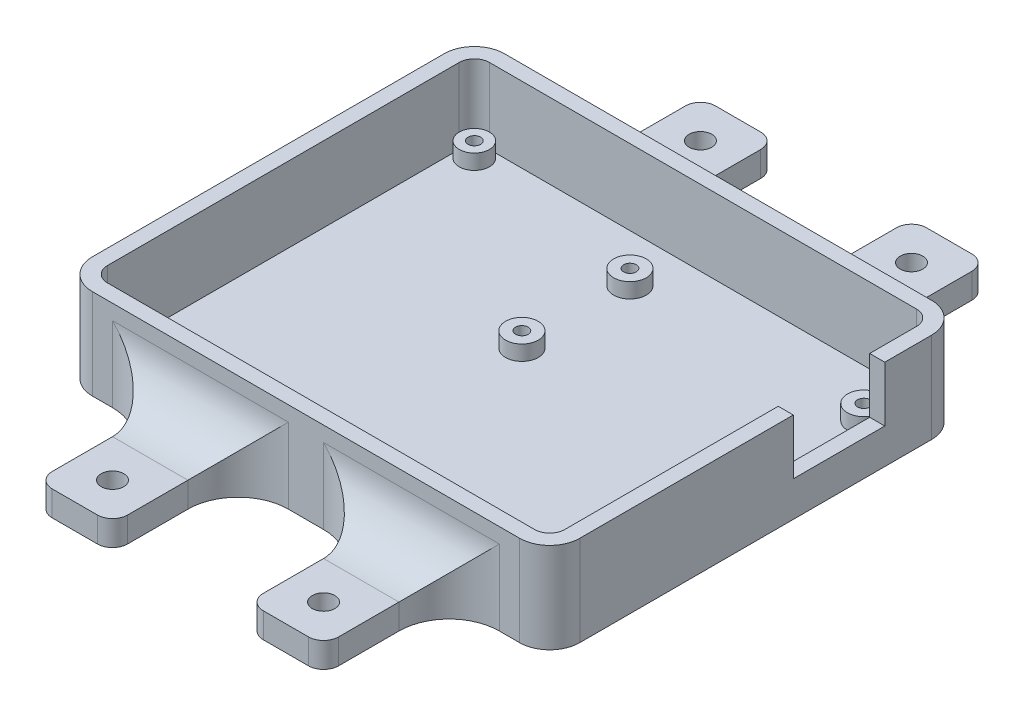
SolidWorks part; units mm, degrees
ref_plane "Front Plane" through (0, 0, 0) normal (0, 0, 1) x (1, 0, 0)
ref_plane "Top Plane" through (0, 0, 0) normal (0, 1, 0) x (1, 0, 0)
ref_plane "Right Plane" through (0, 0, 0) normal (1, 0, 0) x (0, 0, -1)
sketch "Sketch1" plane through (0, 0, 0) normal (0, 1, 0) x (1, 0, 0)
  line L0 (-3, 3) -> (-88, 3)
  line L1 (-3, 0) -> (-88, 0)
  line L2 (0, -3) -> (0, -73)
  line L3 (-3, -76) -> (-88, -76)
  line L4 (-91, -3) -> (-91, -73)
  line L5 (-94, -3) -> (-94, -73)
  line L6 (-3, -79) -> (-88, -79)
  line L7 (3, -3) -> (3, -73)
  circle A0 centre (-3.99, -9.5) radius 1.25
  circle A1 centre (-50.53, -9.5) radius 1.25
  circle A2 centre (-3.99, -31) radius 1.25
  circle A3 centre (-50.53, -31) radius 1.25
  arc A4 (0, -73) -> (-3, -76) centre (-3, -73) cw
  arc A5 (-88, -76) -> (-91, -73) centre (-88, -73) cw
  arc A6 (-88, 0) -> (-91, -3) centre (-88, -3) ccw
  arc A7 (-3, 0) -> (0, -3) centre (-3, -3) cw
  circle A8 centre (-3.99, -9.5) radius 3.25
  circle A9 centre (-3.99, -31) radius 3.25
  circle A10 centre (-50.53, -31) radius 3.25
  circle A11 centre (-50.53, -9.5) radius 3.25
  circle A12 centre (-3, -3) radius 1.25
  circle A13 centre (-88, -3) radius 1.25
  circle A14 centre (-88, -73) radius 1.25
  circle A15 centre (-3, -73) radius 1.25
  circle A16 centre (-3, -3) radius 3
  circle A17 centre (-3, -73) radius 3
  circle A18 centre (-88, -73) radius 3
  circle A19 centre (-88, -3) radius 3
  arc A20 (-88, 3) -> (-94, -3) centre (-88, -3) ccw
  arc A21 (-88, -79) -> (-94, -73) centre (-88, -73) cw
  arc A22 (3, -73) -> (-3, -79) centre (-3, -73) cw
  arc A23 (-3, 3) -> (3, -3) centre (-3, -3) cw
  point P21 (0, -76)
  point P26 (-91, 0)
  point P29 (0, 0)
  dimension "D1" = 2.5
  dimension "D2" = 2.5
  dimension "D3" = 2.5
  dimension "D4" = 2.5
  dimension "D11" = 3
  dimension "D13" = 2.5
  dimension "D14" = 2.5
  dimension "D15" = 2.5
  dimension "D16" = 2.5
  dimension "D5" = 21.5
  dimension "D6" = 46.54
  dimension "D7" = 9.5
  dimension "D8" = 3.99
  dimension "D9" = 76
  dimension "D10" = 91
  dimension "D18" = 3
  dimension "D12" = 2
  dimension "D17" = 1.75
extrude "Boss-Extrude1" add sketch "Sketch1" against normal blind 3 contours L0 A20 L5 A21 L6 A22 L7 A23
extrude "Boss-Extrude2" add sketch "Sketch1<4>" along normal blind 15 contours A23 L0 A20 L5 A21 L6 A22 L7 L1 A7 L2 A4 L3 A5 L4 A6 region at (0.3445, 0, -0.3445)
sketch "Sketch1<4>" plane through (0, 0, 0) normal (0, 1, 0) x (1, 0, 0) same geometry as "Sketch1"
extrude "Boss-Extrude3" add sketch "Sketch1<5>" along normal blind 3 contours A6 A19 A13 | A11 A1 | A10 A3 | A7 A16 A12 | A8 A0 | A9 A2 | A4 A17 A15 | A5 A18 A14 region at (-0.9387, 0, 0.9387) region at (-85.9387, 0, 0.9387) region at (-0.9387, 0, 75.0613) region at (-88, 0, 70.0849) region at (-7.1481, 0, 9.5) region at (-7.1481, 0, 31) region at (-53.6881, 0, 31) region at (-53.6881, 0, 9.5)
sketch "Sketch1<5>" plane through (0, 0, 0) normal (0, 1, 0) x (1, 0, 0) same geometry as "Sketch1"
extrude "Cut-Extrude1" cut sketch "Sketch1<6>" against normal through all contours A13 | A1 | A3 | A12 | A0 | A2 | A15 | A14
sketch "Sketch1<6>" plane through (0, 0, 0) normal (0, 1, 0) x (1, 0, 0) same geometry as "Sketch1"
sketch "Sketch3" plane through (3, 0, 0) normal (1, 0, 0) x (0, 0, -1)
  line L0 (-3, -3) -> (-3, 15) construction
  line L1 (-30.52, 15) -> (-12.32, 15)
  line L2 (-30.52, 15) -> (-30.52, 4)
  line L3 (-30.52, 4) -> (-12.32, 4)
  line L4 (-12.32, 15) -> (-12.32, 4)
  line L5 (-3, -3) -> (-73, -3) construction
  line L6 (-3, 15) -> (-73, 15) construction
  dimension "D1" = 9.32
  dimension "D2" = 18.2
  dimension "D3" = 7
  dimension "D4" = 0
extrude "Cut-Extrude2" cut sketch "Sketch3" against normal up to next
sketch "Sketch4" plane through (0, -3, 0) normal (0, -1, 0) x (1, 0, 0)
  line L0 (-3, 79) -> (-88, 79) construction
  line L1 (-17, 79) -> (-32, 79)
  line L2 (-17, 79) -> (-17, 101)
  line L3 (-20, 104) -> (-29, 104)
  line L4 (-32, 79) -> (-32, 101)
  line L5 (-3, -3) -> (-88, -3) construction
  line L6 (-17, -3) -> (-32, -3)
  line L7 (-17, -3) -> (-17, -25)
  line L8 (-20, -28) -> (-29, -28)
  line L9 (-32, -3) -> (-32, -25)
  line L10 (3, 3) -> (3, 73) construction
  line L11 (-59, 79) -> (-74, 79)
  line L12 (-59, 79) -> (-59, 101)
  line L13 (-62, 104) -> (-71, 104)
  line L14 (-74, 79) -> (-74, 101)
  line L15 (-59, -3) -> (-74, -3)
  line L16 (-59, -3) -> (-59, -25)
  line L17 (-62, -28) -> (-71, -28)
  line L18 (-74, -3) -> (-74, -25)
  line L19 (-94, 3) -> (-94, 73) construction
  arc A0 (-59, 101) -> (-62, 104) centre (-62, 101) ccw
  arc A1 (-71, 104) -> (-74, 101) centre (-71, 101) ccw
  arc A2 (-71, -28) -> (-74, -25) centre (-71, -25) cw
  arc A3 (-59, -25) -> (-62, -28) centre (-62, -25) cw
  arc A4 (-29, -28) -> (-32, -25) centre (-29, -25) cw
  arc A5 (-17, -25) -> (-20, -28) centre (-20, -25) cw
  arc A6 (-29, 104) -> (-32, 101) centre (-29, 101) ccw
  arc A7 (-17, 101) -> (-20, 104) centre (-20, 101) ccw
  circle A8 centre (-24.5, 96.5) radius 2.25
  circle A9 centre (-66.5, 96.5) radius 2.25
  circle A10 centre (-24.5, -20.5) radius 2.25
  circle A11 centre (-66.5, -20.5) radius 2.25
  point P30 (-74, -28)
  point P33 (-59, -28)
  point P36 (-32, -28)
  point P39 (-17, -28)
  point P44 (-17, 104)
  point P53 (0, 0)
  point P54 (0, 0)
  point P55 (0, 0)
  point P56 (0, 0)
  point P59 (-17, 94.2631)
  dimension "D7" = 3
  dimension "D12" = 4.5
  dimension "D13" = 4.5
  dimension "D14" = 4.5
  dimension "D15" = 4.5
  dimension "D1" = 20
  dimension "D2" = 20
  dimension "D3" = 15
  dimension "D4" = 15
  dimension "D5" = 25
  dimension "D6" = 25
  dimension "D8" = 7.5
  dimension "D9" = 7.5
  dimension "D10" = 7.5
  dimension "D11" = 7.5
extrude "Boss-Extrude4" add sketch "Sketch4" against normal blind 5
fillet "Fillet1" radius 10 12 edges at (-17, -0.5, 79) (-24.5, 2, 79) (-32, -0.5, 79) (-59, -0.5, 79) (-66.5, 2, 79) (-74, -0.5, 79) (-74, -0.5, -3) (-17, -0.5, -3) (-32, -0.5, -3) (-59, -0.5, -3) (-66.5, 2, -3) (-24.5, 2, -3)
